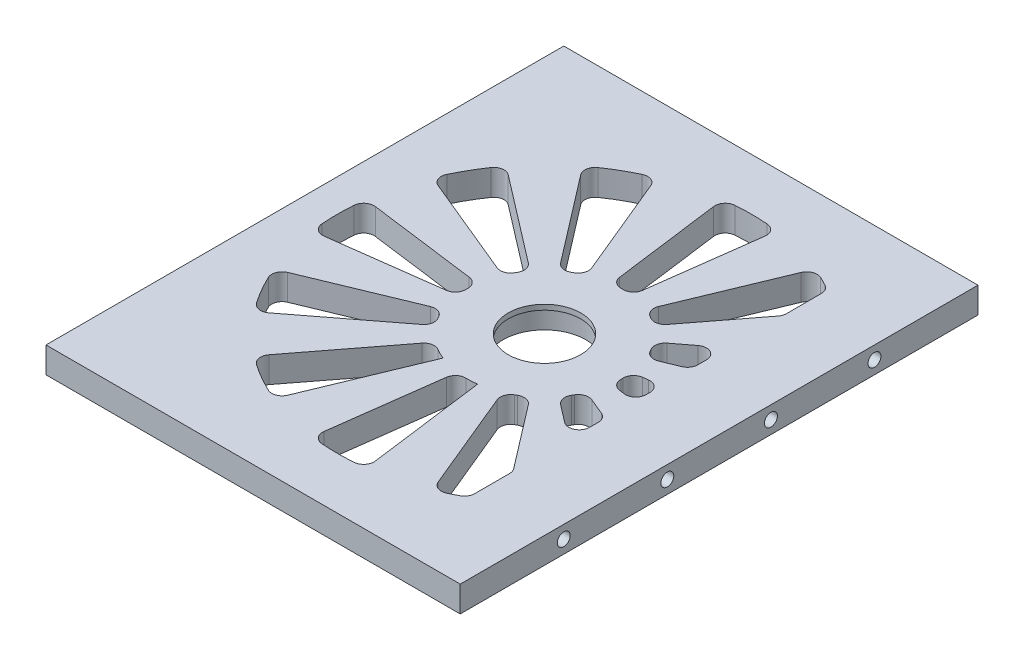
SolidWorks part; units mm, degrees
material "Alliage 2014"
ref_plane "Plan de face" through (0, 0, 0) normal (0, 0, 1) x (1, 0, 0)
ref_plane "Plan de dessus" through (0, 0, 0) normal (0, 1, 0) x (1, 0, 0)
ref_plane "Plan de droite" through (0, 0, 0) normal (1, 0, 0) x (0, 0, -1)
sketch "Esquisse2" plane through (0, 0, 0) normal (0, 1, 0) x (1, 0, 0)
  line L1 (-40, 50) -> (40, 50)
  line L2 (-40, 50) -> (-40, -50)
  line L3 (-40, -50) -> (40, -50)
  line L4 (40, 50) -> (40, -50)
  line L5 (-40, 50) -> (40, -50) construction
  line L6 (-40, -50) -> (40, 50) construction
  circle A0 centre (6.27, 0) radius 7
  point P0 (0, 0)
  dimension "D4" = 14
  dimension "D1" = 80
  dimension "D2" = 100
  dimension "D3" = 33.73
extrude "Boss.-Extru.1" add sketch "Esquisse2" along normal blind 5
hole_wizard "Trou taraudé M3x0.51" positions "Esquisse4" profile "Esquisse3" tap size "M3x0.5" standard "Ansi Métrique"
sketch "Esquisse4" plane through (40, 0, 0) normal (1, 0, 0) x (0, 0, -1)
  line L0 (-50, 0) -> (50, 0) construction
  point P0 (-10, 2.5)
  point P2 (0, 0)
  point P10 (0, 0)
  dimension "D1" = 2.5
  dimension "D2" = 10
sketch "Esquisse3" plane through (40, 2.5, 10) normal (0, 1, 0) x (0, 0, -1)
  line L0 (0, 0) -> (0, 15.7511)
  line L1 (0, 15.7511) -> (1.25, 15)
  line L2 (1.25, 15) -> (1.25, 0)
  line L5 (1.25, 0) -> (0, 0)
  line L10 (0, 15.7511) -> (-1.25, 15) construction
  line L11 (0, -6.35) -> (0, 107.95) construction
  dimension "Diamètre du trou pour taraudage" = 2.5
  dimension "Profondeur du trou pour taraudage" = 15
  dimension "Angle de pointe" = 118
cosmetic thread "Filetage de perçage1" parameters "D1"=8, "D2"=3
pattern_linear "Répétition linéaire1" count 3 spacing 20 along (0, 0, -1) count 2 spacing 20 along (0, 0, 1) of "Trou taraudé M3x0.51"
hole_wizard "Trou taraudé M3x0.52" positions "Esquisse6" profile "Esquisse5" tap size "M3x0.5" standard "Ansi Métrique"
sketch "Esquisse6" plane through (-40, 0, 0) normal (-1, 0, 0) x (0, 0, 1)
  line L0 (-50, 0) -> (50, 0) construction
  point P0 (-10, 2.5)
  point P2 (0, 0)
  point P5 (0, 0)
  dimension "D1" = 10
  dimension "D2" = 2.5
sketch "Esquisse5" plane through (-40, 2.5, -10) normal (0, 1, 0) x (0, 0, 1)
  line L0 (0, 0) -> (0, 15.7511)
  line L1 (0, 15.7511) -> (1.25, 15)
  line L2 (1.25, 15) -> (1.25, 0)
  line L5 (1.25, 0) -> (0, 0)
  line L10 (0, 15.7511) -> (-1.25, 15) construction
  line L11 (0, -6.35) -> (0, 107.95) construction
  dimension "Diamètre du trou pour taraudage" = 2.5
  dimension "Profondeur du trou pour taraudage" = 15
  dimension "Angle de pointe" = 118
cosmetic thread "Filetage de perçage2" parameters "D1"=8, "D2"=3
pattern_linear "Répétition linéaire2" count 3 spacing 20 along (0, 0, 1) count 2 spacing 20 along (0, 0, -1) of "Trou taraudé M3x0.52"
sketch "Esquisse8" plane through (0, 0, 0) normal (0, -1, 0) x (1, 0, 0)
  circle A0 centre (6.27, 0) radius 8
  dimension "D1" = 16
extrude "Enlèv. mat.-Extru.2" cut sketch "Esquisse8" against normal blind 4
sketch "Esquisse9" plane through (0, 0, 0) normal (0, -1, 0) x (1, 0, 0)
  line L0 (26.27, 34.641) -> (26.27, -34.641)
  line L1 (6.27, 0) -> (45.9278, 5.221)
  line L2 (6.27, 0) -> (45.9278, -5.221)
  line L3 (6.27, 0) -> (43.2252, -15.3073)
  line L4 (6.27, 0) -> (38.0041, -24.3505)
  line L5 (6.27, 0) -> (30.6205, -31.7341)
  line L6 (6.27, 0) -> (21.5773, -36.9552)
  line L7 (6.27, 0) -> (11.491, -39.6578)
  line L8 (6.27, 0) -> (1.049, -39.6578)
  line L9 (6.27, 0) -> (-9.0373, -36.9552)
  line L10 (6.27, 0) -> (-18.0805, -31.7341)
  line L11 (6.27, 0) -> (-25.4641, -24.3505)
  line L12 (6.27, 0) -> (-30.6852, -15.3073)
  line L13 (6.27, 0) -> (-33.3878, -5.221)
  line L14 (6.27, 0) -> (-33.3878, 5.221)
  line L15 (6.27, 0) -> (-30.6852, 15.3073)
  line L16 (6.27, 0) -> (-25.4641, 24.3505)
  line L17 (6.27, 0) -> (-18.0805, 31.7341)
  line L18 (6.27, 0) -> (-9.0373, 36.9552)
  line L19 (6.27, 0) -> (1.049, 39.6578)
  line L20 (6.27, 0) -> (11.491, 39.6578)
  line L21 (6.27, 0) -> (21.5773, 36.9552)
  line L22 (6.27, 0) -> (30.6205, 31.7341)
  line L23 (6.27, 0) -> (38.0041, 24.3505)
  line L24 (6.27, 0) -> (43.2252, 15.3073)
  circle A0 centre (6.27, 0) radius 15
  circle A1 centre (6.27, 0) radius 20
  circle A2 centre (6.27, 0) radius 40
  dimension "D1" = 30
  dimension "D2" = 40
  dimension "D3" = 80
  dimension "D4" = 15
  dimension "D5" = 12
extrude "Enlèv. mat.-Extru.3" cut sketch "Esquisse9" against normal blind 10 contours A1 A0 | L24 A1 L23 A0 | A1 L24 L0 L23 | L22 A1 L21 A0 | L0 A2 L21 A1 L22 | L20 A2 L19 A1 | L20 A1 L19 A0 | L18 A2 L17 A1 | L18 A1 L17 A0 | L16 A2 L15 A1 | L16 A1 L15 A0 | L14 A1 L13 A0 | L14 A2 L13 A1 | L12 A2 L11 A1 | L12 A1 L11 A0 | L10 A2 L9 A1 | L10 A1 L9 A0 | L8 A2 L7 A1 | L8 A1 L7 A0 | L6 A2 L0 L5 A1 | L6 A1 L5 A0 | L4 A1 L3 A0 | A1 L4 L0 L3 region at (20.9646, 0, 26.3193) region at (24.8192, 0, 11.4013) region at (15.0544, 0, 15.215) region at (6.27, 0, 31.0223) region at (21.485, 0, 8.7844) region at (6.27, 0, 17.5688) region at (-9.2412, 0, 26.8661) region at (23.8388, 0, 0) region at (21.485, 0, -8.7844) region at (15.0544, 0, -15.215) region at (6.27, 0, -17.5688) region at (-2.5144, 0, -15.215) region at (-8.945, 0, -8.7844) region at (-11.2988, 0, 0) region at (-8.945, 0, 8.7844) region at (-2.5144, 0, 15.215) region at (24.8192, 0, -11.4013) region at (20.9646, 0, -26.3193) region at (6.27, 0, -31.0223) region at (-9.2412, 0, -26.8661) region at (-20.5961, 0, -15.5112) region at (-24.7523, 0, 0) region at (-20.5961, 0, 15.5112)
fillet "Congé1" radius 2 48 edges at (1.049, 2.5, 39.6578) (-9.0373, 2.5, 36.9552) (-18.0805, 2.5, 31.7341) (-25.4641, 2.5, 24.3505) (-33.3878, 2.5, -5.221) (-33.3878, 2.5, 5.221) (-30.6852, 2.5, 15.3073) (-30.6852, 2.5, -15.3073) (-25.4641, 2.5, -24.3505) (8.2279, 2.5, -14.8717) (11.491, 2.5, -39.6578) (-2.8614, 2.5, 11.9003) (-7.5882, 2.5, 5.7403) (-8.6017, 2.5, -1.9579) (-5.6303, 2.5, -9.1314) (11.491, 2.5, 39.6578) (-5.6303, 2.5, 9.1314) (-8.6017, 2.5, 1.9579) (-7.5882, 2.5, -5.7403) (0.5297, 2.5, -13.8582) (-2.8614, 2.5, -11.9003) (-9.0373, 2.5, -36.9552) (-18.0805, 2.5, -31.7341) (1.049, 2.5, -39.6578) (4.3121, 2.5, 14.8717) (12.0103, 2.5, 13.8582) (15.4014, 2.5, 11.9003) (15.4014, 2.5, -11.9003) (4.3121, 2.5, -14.8717) (12.0103, 2.5, -13.8582) (20.1282, 2.5, -5.7403) (21.1417, 2.5, 1.9579) (20.1282, 2.5, 5.7403) (18.1703, 2.5, 9.1314) (21.1417, 2.5, -1.9579) (18.1703, 2.5, -9.1314) (21.5773, 2.5, -36.9552) (26.27, 2.5, -34.641) (26.27, 2.5, -26.0645) (26.27, 2.5, -8.2843) (26.27, 2.5, -15.3465) (26.0989, 2.5, -2.6105) (26.0989, 2.5, 2.6105) (26.27, 2.5, 15.3465) (26.27, 2.5, 8.2843) (26.27, 2.5, 26.0645) (26.27, 2.5, 34.641) (21.5773, 2.5, 36.9552)
